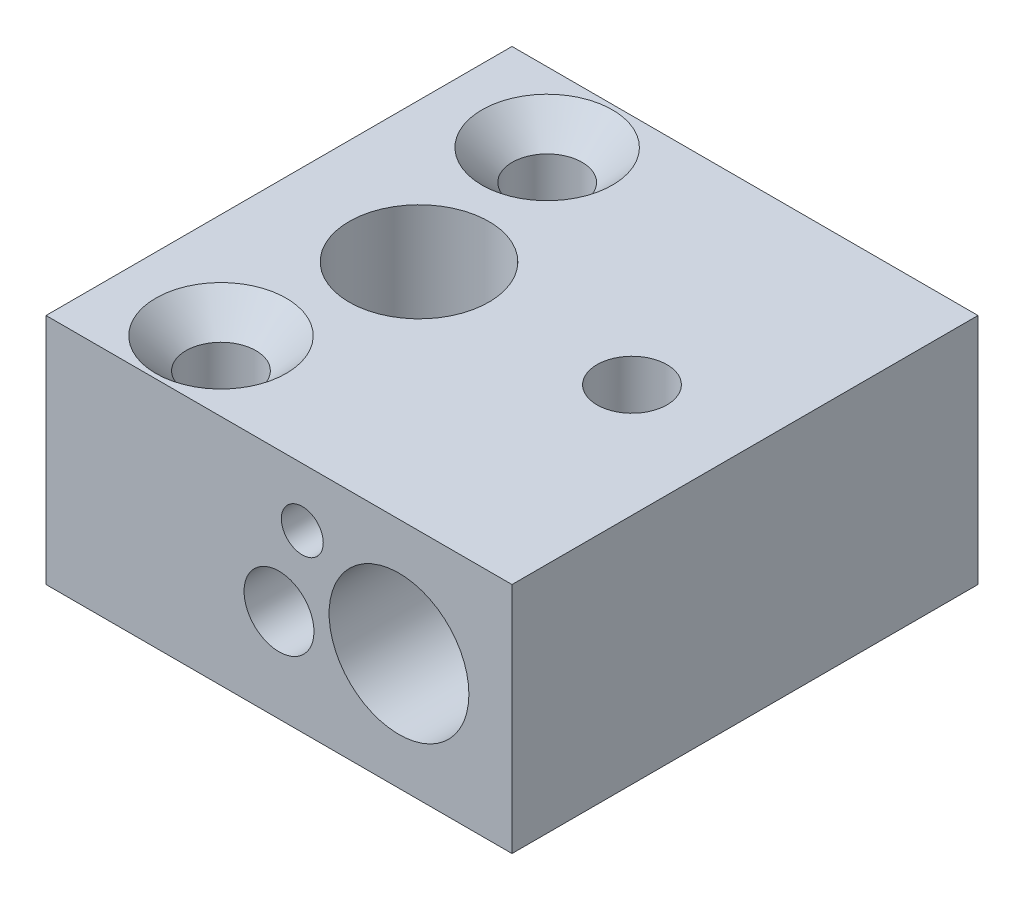
SolidWorks part; units mm, degrees
ref_plane "Płaszczyzna przednia" through (0, 0, 0) normal (0, 0, 1) x (1, 0, 0)
ref_plane "Płaszczyzna górna" through (0, 0, 0) normal (0, 1, 0) x (1, 0, 0)
ref_plane "Płaszczyzna prawa" through (0, 0, 0) normal (1, 0, 0) x (0, 0, -1)
sketch "Sketch1" plane through (0, 0, 0) normal (0, 1, 0) x (1, 0, 0)
  line L1 (0, 0) -> (20, 0)
  line L2 (0, 0) -> (0, 20)
  line L3 (0, 20) -> (20, 20)
  line L4 (20, 0) -> (20, 20)
  dimension "D1" = 20
  dimension "D2" = 20
extrude "Boss-Extrude1" add sketch "Sketch1" along normal blind 10
hole_wizard "Ø6.0mm Dowel Hole2" positions "Sketch2" profile "Sketch3" hole size "Ø6.0" standard "ANSI Metric" end condition through all
sketch "Sketch2" plane through (0, 10, 0) normal (0, 1, 0) x (1, 0, 0)
  line L0 (0, 20) -> (0, 0) construction
  line L2 (0, 0) -> (20, 0) construction
  point P0 (6.01, 10)
  dimension "D1" = 6.01
  dimension "D2" = 10
sketch "Sketch3" plane through (6.01, 10, -10) normal (1, 0, 0) x (0, 0, 1)
  line L0 (0, 0) -> (0, 10)
  line L1 (0, 10) -> (3, 10)
  line L2 (3, 10) -> (3, 0)
  line L5 (3, 0) -> (0, 0)
  line L11 (0, -6.35) -> (0, 107.95) construction
  dimension "Thru Hole Dia." = 6
  dimension "Thru Hole Depth" = 10
hole_wizard "CSK for M3 Flat Head Machine Screw1" positions "Sketch4" profile "Sketch5" countersink size "M3" standard "ANSI Metric" end condition through all
sketch "Sketch4" plane through (0, 10, 0) normal (0, 1, 0) x (1, 0, 0)
  line L1 (0, 0) -> (20, 0) construction
  circle A1 centre (6.01, 10) radius 3 construction
  point P0 (4.51, 3)
  point P2 (4.51, 17)
  dimension "D1" = 1.5
  dimension "D2" = 14
  dimension "D3" = 3
sketch "Sketch5" plane through (4.51, 10, -3) normal (1, 0, 0) x (0, 0, 1)
  line L0 (0, 0) -> (0, 10)
  line L1 (0, 10) -> (1.5, 10)
  line L2 (1.5, 10) -> (1.5, 1.3)
  line L3 (1.5, 1.3) -> (2.8, 0)
  line L5 (2.8, 0) -> (0, 0)
  line L6 (-1.5, 1.3) -> (-2.8, 0) construction
  line L11 (0, -6.35) -> (0, 107.95) construction
  dimension "Thru Hole Dia." = 3
  dimension "Thru Hole Depth" = 10
  dimension "Near C'Sink Dia." = 5.6
  dimension "Near C'Sink Angle" = 90
hole_wizard "Ø6.0mm Dowel Hole3" positions "Sketch6" profile "Sketch8" hole size "Ø6.0" standard "ANSI Metric" end condition through all
sketch "Sketch6" plane through (0, 0, 0) normal (0, 0, 1) x (1, 0, 0)
  line L0 (0, 10) -> (20, 10) construction
  line L2 (20, 10) -> (20, 0) construction
  point P0 (15.15, 5)
  dimension "D1" = 5
  dimension "D2" = 4.85
sketch "Sketch8" plane through (15.15, 5, 0) normal (1, 0, 0) x (0, -1, 0)
  line L0 (0, 0) -> (0, 20)
  line L1 (0, 20) -> (3, 20)
  line L2 (3, 20) -> (3, 0)
  line L5 (3, 0) -> (0, 0)
  line L11 (0, -6.35) -> (0, 107.95) construction
  dimension "Thru Hole Dia." = 6
  dimension "Thru Hole Depth" = 20
hole_wizard "Ø3.0mm Dowel Hole1" positions "Sketch9" profile "Sketch10" hole size "Ø3.0" standard "ANSI Metric" end condition up to next
sketch "Sketch9" plane through (0, 10, 0) normal (0, 1, 0) x (1, 0, 0)
  line L0 (20, 0) -> (20, 20) construction
  line L1 (0, 0) -> (20, 0) construction
  point P0 (15.15, 10)
  dimension "D1" = 4.85
  dimension "D2" = 10
sketch "Sketch10" plane through (15.15, 10, -10) normal (1, 0, 0) x (0, 0, 1)
  line L0 (0, 0) -> (0, 2)
  line L1 (0, 2) -> (1.5, 2)
  line L2 (1.5, 2) -> (1.5, 0)
  line L5 (1.5, 0) -> (0, 0)
  line L11 (0, -6.35) -> (0, 107.95) construction
  dimension "Thru Hole Dia." = 3
  dimension "Thru Hole Depth" = 2
hole_wizard "Ø3.0mm Dowel Hole2" positions "Sketch13" profile "Sketch14" hole size "Ø3.0" standard "ANSI Metric"
sketch "Sketch13" plane through (0, 0, 0) normal (0, 0, 1) x (1, 0, 0)
  line L0 (20, 10) -> (20, 0) construction
  circle A0 centre (15.15, 5) radius 3 construction
  point P0 (10, 4)
  dimension "D1" = 1
  dimension "D2" = 10
sketch "Sketch14" plane through (10, 4, 0) normal (1, 0, 0) x (0, -1, 0)
  line L0 (0, 0) -> (0, 6.9013)
  line L1 (0, 6.9013) -> (1.5, 6)
  line L2 (1.5, 6) -> (1.5, 0)
  line L5 (1.5, 0) -> (0, 0)
  line L10 (0, 6.9013) -> (-1.5, 6) construction
  line L11 (0, -6.35) -> (0, 107.95) construction
  dimension "Hole Dia." = 3
  dimension "Hole Depth" = 6
  dimension "Drill Angle" = 118
hole_wizard "Ø1.5mm Dowel Hole1" positions "Sketch15" profile "Sketch16" hole size "Ø1.5" standard "ANSI Metric"
sketch "Sketch15" plane through (0, 0, 0) normal (0, 0, 1) x (1, 0, 0)
  line L0 (20, 10) -> (20, 0) construction
  line L1 (0, 10) -> (20, 10) construction
  point P0 (11, 7.5)
  dimension "D1" = 9
  dimension "D2" = 2.5
sketch "Sketch16" plane through (11, 7.5, 0) normal (1, 0, 0) x (0, -1, 0)
  line L0 (0, 0) -> (0, 4.5408)
  line L1 (0, 4.5408) -> (0.9, 4)
  line L2 (0.9, 4) -> (0.9, 0)
  line L5 (0.9, 0) -> (0, 0)
  line L10 (0, 4.5408) -> (-0.9, 4) construction
  line L11 (0, -6.35) -> (0, 107.95) construction
  dimension "Hole Dia." = 1.8
  dimension "Hole Depth" = 4
  dimension "Drill Angle" = 118
